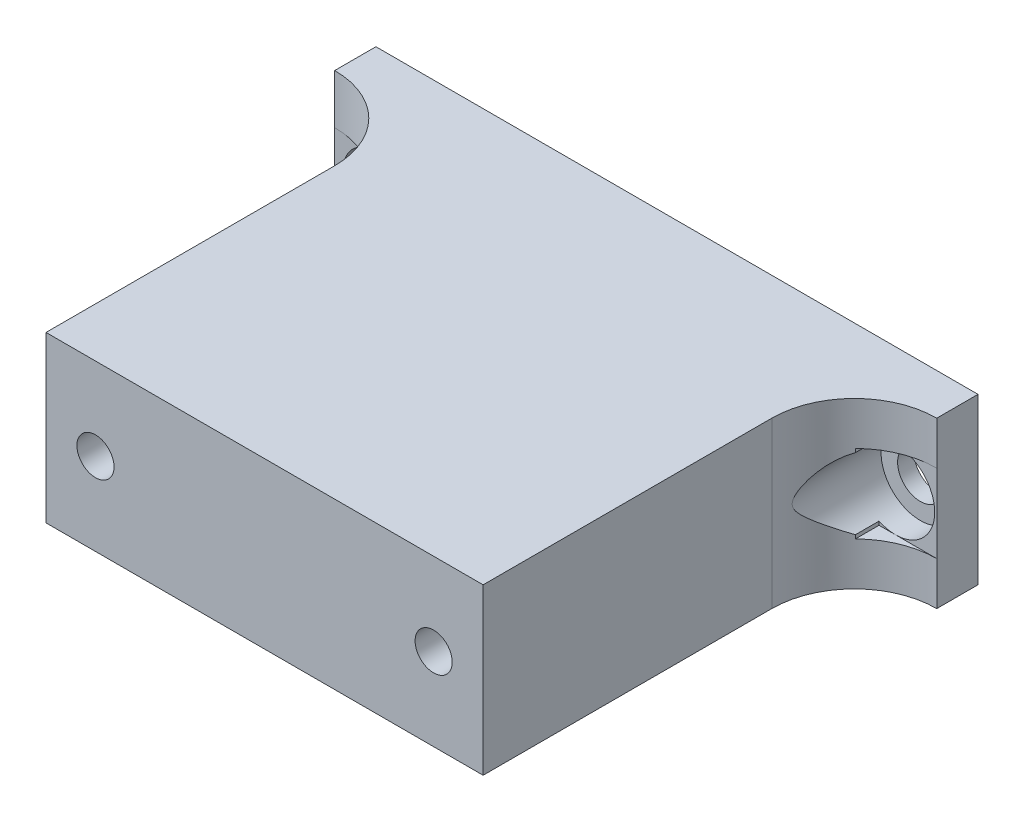
SolidWorks part; units mm, degrees
ref_plane "정면" through (0, 0, 0) normal (0, 0, 1) x (1, 0, 0)
ref_plane "윗면" through (0, 0, 0) normal (0, 1, 0) x (1, 0, 0)
ref_plane "우측면" through (0, 0, 0) normal (1, 0, 0) x (0, 0, -1)
sketch "스케치1" plane through (0, 0, 0) normal (0, 0, 1) x (1, 0, 0)
  line L1 (-26.5, 10) -> (26.5, 10)
  line L2 (-26.5, 10) -> (-26.5, -10)
  line L3 (-26.5, -10) -> (26.5, -10)
  line L4 (26.5, 10) -> (26.5, -10)
  line L5 (-26.5, 10) -> (26.5, -10) construction
  line L6 (-26.5, -10) -> (26.5, 10) construction
  point P0 (0, 0)
  dimension "D1" = 20
  dimension "D2" = 53
extrude "보스-돌출1" add sketch "스케치1" along normal blind 50
hole_wizard "M5 나사 구멍1" positions "스케치2" profile "스케치3" tap size "M5" standard "KS"
sketch "스케치2" plane through (0, 0, 50) normal (0, 0, 1) x (1, 0, 0)
  line L0 (-26.5, 10) -> (-26.5, -10) construction
  line L1 (26.5, -10) -> (26.5, 10) construction
  point P0 (20.5, 0)
  point P2 (-20.5, 0)
  dimension "D1" = 6
  dimension "D2" = 6
sketch "스케치3" plane through (20.5, 0, 50) normal (1, 0, 0) x (0, -1, 0)
  line L0 (0, 0) -> (0, 46.3519)
  line L1 (0, 46.3519) -> (2.25, 45)
  line L2 (2.25, 45) -> (2.25, 0)
  line L5 (2.25, 0) -> (0, 0)
  line L10 (0, 46.3519) -> (-2.25, 45) construction
  line L11 (0, -6.35) -> (0, 107.95) construction
  dimension "탭 드릴 지름" = 4.5
  dimension "탭 드릴 깊이" = 45
  dimension "드릴 각도" = 118
sketch "스케치4" plane through (-26.5, 0, 0) normal (-1, 0, 0) x (0, 0, 1)
  line L0 (50, -10) -> (0, -10) construction
  line L1 (0, 10) -> (5, 10)
  line L2 (0, 10) -> (0, -10)
  line L3 (0, -10) -> (5, -10)
  line L4 (5, 10) -> (5, -10)
  dimension "D1" = 5
extrude "보스-돌출2" add sketch "스케치4" along normal blind 20
hole_wizard "M4 소켓 머리 캡 나사용 카운터보어1" positions "스케치5" profile "스케치6" counterbore size "M4" standard "KS"
sketch "스케치5" plane through (0, 0, 5) normal (0, 0, 1) x (1, 0, 0)
  line L0 (-46.5, -10) -> (-46.5, 10) construction
  line L1 (-46.5, 10) -> (-26.5, 10) construction
  point P0 (-31.5, 0)
  dimension "D1" = 15
  dimension "D2" = 10
sketch "스케치6" plane through (-31.5, 0, 5) normal (1, 0, 0) x (0, -1, 0)
  line L0 (0, 0) -> (0, 16.3519)
  line L1 (0, 16.3519) -> (2.25, 15)
  line L2 (2.25, 15) -> (2.25, 3)
  line L3 (2.25, 3) -> (4, 3)
  line L4 (4, 3) -> (4, 0)
  line L5 (4, 0) -> (0, 0)
  line L10 (0, 16.3519) -> (-2.25, 15) construction
  line L11 (0, -6.35) -> (0, 107.95) construction
  dimension "구멍 지름" = 4.5
  dimension "구멍 깊이" = 15
  dimension "카운터보어 지름" = 8
  dimension "카운터보어 깊이" = 3
  dimension "드릴 각도" = 118
sketch "스케치7" plane through (26.5, 0, 0) normal (1, 0, 0) x (0, 0, -1)
  line L0 (-50, -10) -> (0, -10) construction
  line L1 (0, 10) -> (-5, 10)
  line L2 (0, 10) -> (0, -10)
  line L3 (0, -10) -> (-5, -10)
  line L4 (-5, 10) -> (-5, -10)
  dimension "D1" = 5
extrude "보스-돌출3" add sketch "스케치7" along normal blind 20
hole_wizard "M5 소켓 머리 캡 나사용 카운터보어1" positions "스케치8" profile "스케치9" counterbore size "M5" standard "KS"
sketch "스케치8" plane through (0, 0, 5) normal (0, 0, 1) x (1, 0, 0)
  line L0 (46.5, 10) -> (26.5, 10) construction
  line L1 (46.5, 10) -> (46.5, -10) construction
  point P0 (31.5, 0)
  dimension "D1" = 10
  dimension "D2" = 15
sketch "스케치9" plane through (31.5, 0, 5) normal (1, 0, 0) x (0, -1, 0)
  line L0 (0, 0) -> (0, 16.6524)
  line L1 (0, 16.6524) -> (2.75, 15)
  line L2 (2.75, 15) -> (2.75, 3)
  line L3 (2.75, 3) -> (4.75, 3)
  line L4 (4.75, 3) -> (4.75, 0)
  line L5 (4.75, 0) -> (0, 0)
  line L10 (0, 16.6524) -> (-2.75, 15) construction
  line L11 (0, -6.35) -> (0, 107.95) construction
  dimension "구멍 지름" = 5.5
  dimension "구멍 깊이" = 15
  dimension "카운터보어 지름" = 9.5
  dimension "카운터보어 깊이" = 3
  dimension "드릴 각도" = 118
fillet "필렛1" radius 10 2 edges at (26.5, 0, 5) (-26.5, 0, 5)
sketch "스케치10" plane through (0, 0, 5) normal (0, 0, 1) x (1, 0, 0)
  line L0 (-36.5, -10) -> (-36.5, 10) construction
  line L1 (-36.5, 4) -> (-30.5, 4)
  line L2 (-36.5, 4) -> (-36.5, -4)
  line L3 (-36.5, -4) -> (-30.5, -4)
  line L4 (-30.5, 4) -> (-30.5, -4)
  line L5 (29.5, 4.75) -> (29.5, -4.75)
  line L6 (36.5, -4.75) -> (29.5, -4.75)
  line L7 (36.5, 4.75) -> (36.5, -4.75)
  line L8 (36.5, 4.75) -> (29.5, 4.75)
  line L9 (36.5, 10) -> (36.5, -10) construction
  circle A0 centre (31.5, 0) radius 4.75 construction
  circle A1 centre (-31.5, 0) radius 4 construction
  dimension "D1" = 6
  dimension "D2" = 7
extrude "컷-돌출1" cut sketch "스케치10" along normal blind 20
sketch "스케치11" plane through (0, 0, 5) normal (0, 0, 1) x (1, 0, 0)
  line L1 (-46.5, 10) -> (-36.5, 10)
  line L2 (-46.5, 10) -> (-46.5, -10)
  line L3 (-46.5, -10) -> (-36.5, -10)
  line L4 (-36.5, 10) -> (-36.5, -10)
  line L5 (46.5, 10) -> (36.5, 10)
  line L6 (46.5, 10) -> (46.5, -10)
  line L7 (46.5, -10) -> (36.5, -10)
  line L8 (36.5, 10) -> (36.5, -10)
extrude "컷-돌출2" cut sketch "스케치11" against normal blind 10
